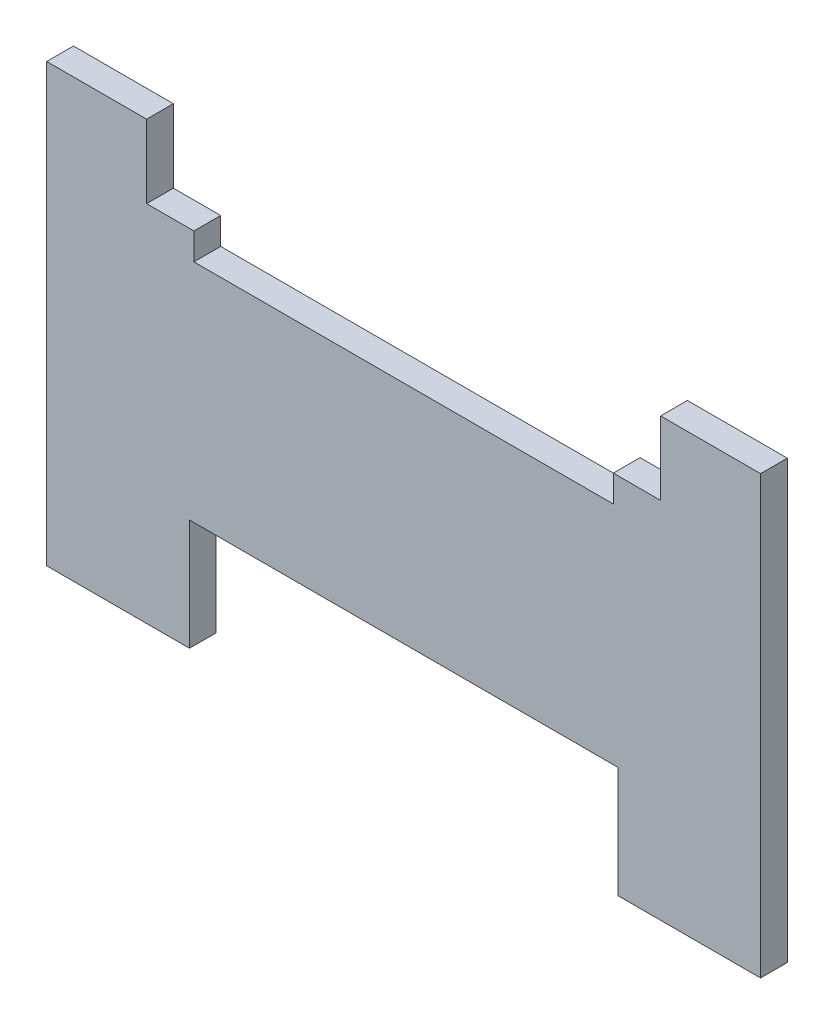
SolidWorks part; units mm, degrees
ref_plane "Front Plane" through (0, 0, 0) normal (0, 0, 1) x (1, 0, 0)
ref_plane "Top Plane" through (0, 0, 0) normal (0, 1, 0) x (1, 0, 0)
ref_plane "Right Plane" through (0, 0, 0) normal (1, 0, 0) x (0, 0, -1)
sketch "Sketch1" plane through (0, 0, 0) normal (0, 0, 1) x (1, 0, 0)
  line L0 (0, 52.125) -> (11.2, 52.125)
  line L1 (80, 52.125) -> (80, 3.175)
  line L2 (80, 3.175) -> (64, 3.175)
  line L3 (64, 3.175) -> (64, 15.625)
  line L4 (64, 15.625) -> (16, 15.625)
  line L5 (16, 15.625) -> (16, 3.175)
  line L6 (16, 3.175) -> (0, 3.175)
  line L7 (0, 3.175) -> (0, 52.125)
  line L8 (16, 3.175) -> (0, 3.175) construction
  line L9 (0, 15.625) -> (80, 15.625) construction
  line L10 (16, 18.625) -> (16, 3.175) construction
  line L11 (64, 18.625) -> (64, 3.175) construction
  line L12 (80, 3.175) -> (80, 52.125) construction
  line L13 (0, 3.175) -> (0, 52.125) construction
  line L15 (40, 15.625) -> (40, 52.125) construction
  line L16 (40, 0) -> (40, 67.125) construction
  line L17 (3, 49.125) -> (3, 6.175) construction
  line L18 (3, 6.175) -> (16, 6.175) construction
  line L19 (64, 6.175) -> (77, 6.175) construction
  line L20 (77, 6.175) -> (77, 49.125) construction
  line L21 (77, 49.125) -> (3, 49.125) construction
  line L22 (0, 18.625) -> (80, 18.625) construction
  line L23 (64, 15.625) -> (80, 15.625) construction
  line L24 (16, 15.625) -> (0, 15.625) construction
  line L25 (8, 3.175) -> (8, 6.175) construction
  line L26 (72, 3.175) -> (72, 6.175) construction
  line L27 (77, 6.175) -> (77, 49.125) construction
  line L28 (77, 6.175) -> (64, 6.175) construction
  line L29 (72, 3.175) -> (72, 6.175) construction
  line L30 (16, 6.175) -> (3, 6.175) construction
  line L31 (3, 6.175) -> (3, 49.125) construction
  line L32 (8, 3.175) -> (8, 6.175) construction
  line L33 (80, 18.625) -> (0, 18.625) construction
  line L34 (77, 49.125) -> (3, 49.125) construction
  line L35 (45.3, 50.175) -> (45.3, 8.175) construction
  line L36 (45.3, 8.175) -> (42.3, 8.175) construction
  line L37 (42.3, 50.175) -> (42.3, 8.175) construction
  line L38 (45.3, 50.175) -> (42.3, 50.175) construction
  line L39 (45.3, 50.175) -> (45.3, 8.175) construction
  line L40 (45.3, 8.175) -> (42.3, 8.175) construction
  line L41 (42.3, 50.175) -> (42.3, 8.175) construction
  line L42 (45.3, 50.175) -> (42.3, 50.175) construction
  line L43 (71.8, 40.925) -> (71.8, 52.125) construction
  line L44 (0, 52.125) -> (80, 52.125) construction
  line L45 (8.2, 52.125) -> (8.2, 40.925) construction
  line L46 (8.2, 40.925) -> (71.8, 40.925) construction
  line L47 (71.8, 52.125) -> (71.8, 40.925) construction
  line L48 (8.2, 40.925) -> (8.2, 52.125) construction
  line L49 (16.5, 40.925) -> (8.2, 40.925) construction
  line L50 (8.2, 52.125) -> (16.5, 52.125) construction
  line L51 (11.2, 49.125) -> (11.2, 43.925) construction
  line L53 (11.2, 52.125) -> (11.2, 43.925)
  line L54 (11.2, 43.925) -> (68.8, 43.925) construction
  line L55 (68.8, 52.125) -> (68.8, 43.925)
  line L56 (68.8, 52.125) -> (80, 52.125)
  line L57 (68.8, 49.125) -> (68.8, 43.925) construction
  line L59 (68.8, 43.925) -> (63.5, 43.925) construction
  line L60 (16.5, 52.125) -> (16.5, 49.125) construction
  line L61 (16.5, 43.925) -> (16.5, 40.925)
  line L62 (16.5, 52.125) -> (16.5, 49.125) construction
  line L63 (63.5, 52.125) -> (63.5, 49.125) construction
  line L64 (63.5, 43.925) -> (63.5, 40.925)
  line L65 (63.5, 52.125) -> (63.5, 49.125) construction
  line L66 (48.3, 53.175) -> (48.3, 5.175) construction
  line L67 (48.3, 5.175) -> (39.3, 5.175) construction
  line L70 (39.3, 53.175) -> (39.3, 5.175) construction
  line L71 (48.3, 53.175) -> (39.3, 53.175) construction
  line L72 (63.5, 43.925) -> (68.8, 43.925)
  line L73 (11.2, 43.925) -> (16.5, 43.925)
  line L74 (39.3, 53.175) -> (39.3, 44.225) construction
  line L80 (16.5, 40.925) -> (63.5, 40.925)
sketch "Sketch2" plane through (0, 0, 0) normal (1, 0, 0) x (0, 0, -1)
  line L1 (0, 52.125) -> (3, 52.125)
  line L2 (0, 52.125) -> (0, 3.175)
  line L3 (0, 3.175) -> (3, 3.175)
  line L4 (3, 52.125) -> (3, 3.175)
extrude "Boss-Extrude1" add sketch "Sketch1" against normal up to vertex (3 mm away) up to point (0, 52.125, -3)
